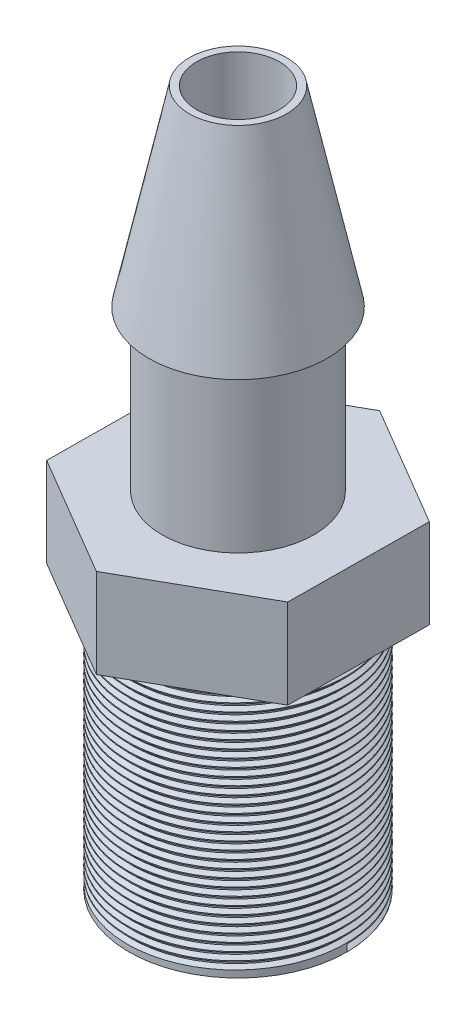
SolidWorks part; units mm, degrees
ref_plane "Front Plane" through (0, 0, 0) normal (0, 0, 1) x (1, 0, 0)
ref_plane "Top Plane" through (0, 0, 0) normal (0, 1, 0) x (1, 0, 0)
ref_plane "Right Plane" through (0, 0, 0) normal (1, 0, 0) x (0, 0, -1)
sketch "Sketch2" plane through (0, 0, 0) normal (0, 1, 0) x (1, 0, 0)
  line L1 (4.8144, -2.8367) -> (4.8639, 2.7511)
  line L2 (4.8639, 2.7511) -> (0.0495, 5.5878)
  line L3 (0.0495, 5.5878) -> (-4.8144, 2.8367)
  line L4 (-4.8144, 2.8367) -> (-4.8639, -2.7511)
  line L5 (-4.8639, -2.7511) -> (-0.0495, -5.5878)
  line L6 (-0.0495, -5.5878) -> (4.8144, -2.8367)
  circle A0 centre (0, 0) radius 5.588 construction
  dimension "D1" = 11.176
extrude "Boss-Extrude1" add sketch "Sketch2" along normal blind 3.556
sketch "Sketch3" plane through (0, 3.556, 0) normal (0, 1, 0) x (1, 0, 0)
  circle A0 centre (0, 0) radius 3.0226
  dimension "D1" = 6.0452
extrude "Boss-Extrude2" add sketch "Sketch3" along normal blind 6.35 contours A0
sketch "Sketch8" plane through (0, 0, 0) normal (0, -1, 0) x (-1, 0, 0)
  circle A0 centre (0, 0) radius 4.3434
  dimension "D1" = 8.6868
extrude "Boss-Extrude3" add sketch "Sketch8" along normal blind 10.16
sketch "Sketch9" plane through (0, 9.906, 0) normal (0, 1, 0) x (1, 0, 0)
  circle A0 centre (0, 0) radius 3.556
  dimension "D1" = 7.112
extrude "Boss-Extrude4" add sketch "Sketch9" along normal blind 7.62
sketch "Sketch10" plane through (0, 17.526, 0) normal (0, 1, 0) x (1, 0, 0)
  circle A0 centre (0, 0) radius 1.651
  dimension "D1" = 3.302
draft "Draft1" type of draft neutral plane draft angle 12 faces to draft 1 face at (0, 17.526, 3.556) neutral plane through (0, 9.906, 0) neutral plane normal (0, -1, 0) reverse direction yes parameters "D1"=12
extrude "Cut-Extrude1" cut sketch "Sketch10" against normal blind 7.62 contours A0
sketch "Sketch11" plane through (0, -10.16, 0) normal (0, -1, 0) x (1, 0, 0)
  circle A0 centre (0, 0) radius 2.667
  dimension "D1" = 5.334
extrude "Cut-Extrude2" cut sketch "Sketch11" against normal blind 7.62
thread "Thread1" pitch 0.3175 method cut profile "Thread Profile1" start angle 0, offset 0, length 0, pitch 0.3175, diameter 8.6868
ref_plane "Plane1" through (4.3434, -10.16, 0) normal (0, 0, 1) x (1, 0, 0)
sketch "Thread Profile1" plane through (4.3434, -10.16, 0) normal (0, 0, 1) x (1, 0, 0)
  line L0 (0, 0) -> (0, 0.3175) construction
  line L11 (0, 0) -> (0, 0.2778)
  line L12 (0, 0.2778) -> (-0.1719, 0.1786)
  line L13 (-0.1719, 0.1786) -> (-0.1719, 0.0992)
  line L15 (-0.1719, 0.0992) -> (0, 0)
  line L17 (-0.1719, 0.1389) -> (0, 0.1389) construction
  point P2 (0, 0)
  dimension "Pitch" = 0.3175
  dimension "Profile_Angle" = 60
  dimension "Profile_Land" = 0.0794
  dimension "Profile_Height" = 0.1719
